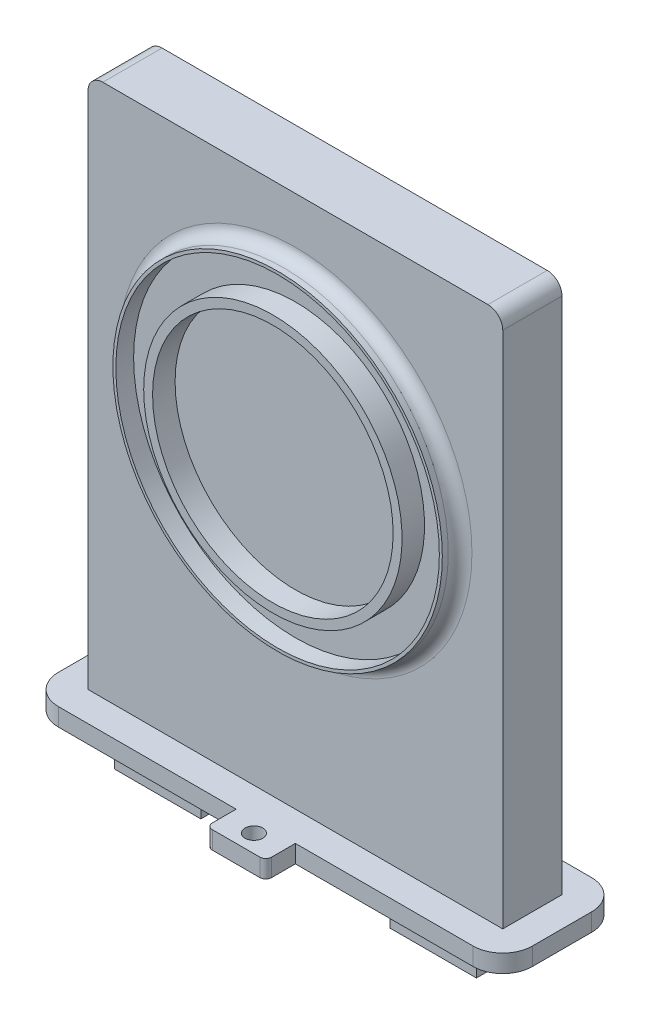
SolidWorks part; units mm, degrees
ref_plane "Front Plane" through (0, 0, 0) normal (0, 0, 1) x (1, 0, 0)
ref_plane "Top Plane" through (0, 0, 0) normal (0, 1, 0) x (1, 0, 0)
ref_plane "Right Plane" through (0, 0, 0) normal (1, 0, 0) x (0, 0, -1)
sketch "Sketch1" plane through (0, 0, 0) normal (0, 0, 1) x (1, 0, 0)
  line L1 (-35, 55.35) -> (35, 55.35)
  line L2 (-35, 55.35) -> (-35, -55.35)
  line L3 (-35, -55.35) -> (35, -55.35)
  line L4 (35, 55.35) -> (35, -55.35)
  line L5 (-35, 55.35) -> (35, -55.35) construction
  line L6 (-35, -55.35) -> (35, 55.35) construction
  point P0 (0, 0)
  dimension "D1" = 70
  dimension "D2" = 110.7
extrude "Boss-Extrude1" add sketch "Sketch1" along normal blind 10
sketch "Sketch3" plane through (0, 0, 0) normal (0, 0, -1) x (-1, 0, 0)
  line L0 (0, -55.35) -> (0, -45) construction
  line L1 (35, -55.35) -> (-35, -55.35) construction
  line L2 (-35, 55.35) -> (35, 55.35) construction
  line L7 (-35, -55.35) -> (-35, 55.35) construction
  line L8 (20.95, -57.2) -> (25.55, -57.2) construction
  line L9 (-20.95, -59.05) -> (-15.95, -59.05)
  line L10 (-30.55, -59.05) -> (-25.55, -59.05)
  line L11 (-30.55, -59.05) -> (-30.55, -61.75)
  line L12 (-30.55, -61.75) -> (-15.95, -61.75)
  line L13 (-15.95, -59.05) -> (-15.95, -61.75)
  line L14 (-30.55, -59.05) -> (-15.95, -61.75) construction
  line L15 (-30.55, -61.75) -> (-15.95, -59.05) construction
  line L16 (-25.55, -55.35) -> (-20.95, -55.35)
  line L17 (-25.55, -55.35) -> (-25.55, -59.05)
  line L19 (-20.95, -55.35) -> (-20.95, -59.05)
  line L20 (-25.55, -55.35) -> (-20.95, -59.05) construction
  line L21 (-25.55, -59.05) -> (-20.95, -55.35) construction
  line L22 (30.55, -59.05) -> (30.55, -61.75)
  line L23 (30.55, -61.75) -> (15.95, -61.75)
  line L24 (15.95, -59.05) -> (15.95, -61.75)
  line L25 (20.95, -59.05) -> (15.95, -59.05)
  line L26 (20.95, -55.35) -> (20.95, -59.05)
  line L27 (25.55, -55.35) -> (20.95, -55.35)
  line L28 (25.55, -55.35) -> (25.55, -59.05)
  line L29 (30.55, -59.05) -> (25.55, -59.05)
  point P5 (0, -50.175)
  point P12 (-23.25, -60.4)
  point P17 (-23.25, -57.2)
  dimension "D1" = 110.7
  dimension "D2" = 11.75
  dimension "D3" = 2.7
  dimension "D4" = 14.6
  dimension "D5" = 4.6
  dimension "D6" = 3.7
extrude "Boss-Extrude3" add sketch "Sketch3" against normal blind 10
sketch "Sketch4" plane through (0, -55.35, 0) normal (0, -1, 0) x (1, 0, 0)
  line L0 (0, 10) -> (0, 0) construction
  line L1 (-20.95, 10) -> (20.95, 10) construction
  line L2 (5, -5) -> (35, -5)
  line L3 (-35, 10) -> (35, 10)
  line L4 (-35, 10) -> (-35, 0)
  line L5 (-35, 0) -> (35, 0)
  line L6 (35, 10) -> (35, 0)
  line L7 (-35, 10) -> (35, 0) construction
  line L8 (-35, 0) -> (35, 10) construction
  line L9 (-35, 15) -> (-5, 15)
  line L10 (-40, 10) -> (-40, 0)
  line L11 (-35, -5) -> (-5, -5)
  line L12 (40, 10) -> (40, 0)
  line L13 (-40, 15) -> (40, -5) construction
  line L14 (-40, -5) -> (40, 15) construction
  line L16 (-5, -5) -> (-5, -9)
  line L17 (-4, -10) -> (4, -10)
  line L18 (5, -5) -> (5, -9)
  line L20 (-40, 5) -> (40, 5) construction
  line L21 (-5, 15) -> (-5, 19)
  line L22 (5, 15) -> (5, 19)
  line L23 (-4, 20) -> (4, 20)
  line L24 (5, 15) -> (35, 15)
  arc A0 (35, 15) -> (40, 10) centre (35, 10) cw
  arc A1 (35, -5) -> (40, 0) centre (35, 0) ccw
  arc A2 (-40, 0) -> (-35, -5) centre (-35, 0) ccw
  arc A3 (-35, 15) -> (-40, 10) centre (-35, 10) ccw
  circle A4 centre (0, -7) radius 1.5
  arc A5 (-5, -9) -> (-4, -10) centre (-4, -9) ccw
  arc A6 (4, -10) -> (5, -9) centre (4, -9) ccw
  circle A7 centre (0, 17) radius 1.5
  arc A8 (-5, 19) -> (-4, 20) centre (-4, 19) cw
  arc A9 (4, 20) -> (5, 19) centre (4, 19) cw
  point P5 (0, 5)
  point P11 (0, 5)
  point P37 (-5, -10)
  dimension "D3" = 5
  dimension "D6" = 3
  dimension "D7" = 1
  dimension "D1" = 20
  dimension "D2" = 80
  dimension "D4" = 5
  dimension "D5" = 10
  dimension "D8" = 3
extrude "Boss-Extrude4" add sketch "Sketch4" against normal blind 3
sketch "Sketch5" plane through (0, 0, 10) normal (0, 0, 1) x (1, 0, 0)
  circle A0 centre (0, 0) radius 27.8
  circle A1 centre (0, 0) radius 27.3
  dimension "D1" = 54.6
  dimension "D2" = 55.6
extrude "Boss-Extrude5" add sketch "Sketch5" along normal blind 3
fillet "Fillet2" radius 2 1 edges at (27.8, 0, 10)
sketch "Sketch10" plane through (0, 0, 10) normal (0, 0, 1) x (1, 0, 0)
  circle A0 centre (0, 0) radius 21.8
  circle A1 centre (0, 0) radius 20.3
  dimension "D1" = 43.6
  dimension "D2" = 40.6
extrude "Boss-Extrude7" add sketch "Sketch10" along normal blind 3.8
sketch "Sketch11" plane through (0, 0, 10) normal (0, 0, 1) x (1, 0, 0)
  line L1 (-35, -52.35) -> (35, -52.35)
  line L2 (-35, -52.35) -> (-35, 37.65)
  line L3 (-35, 37.65) -> (35, 37.65)
  line L4 (35, -52.35) -> (35, 37.65)
  line L9 (-35, -52.35) -> (35, -52.35)
  line L10 (-35, -52.35) -> (-35, 55.35)
  line L11 (-35, 55.35) -> (35, 55.35)
  line L12 (35, -52.35) -> (35, 55.35)
  line M5 (35, -52.35) -> (35, 55.35)
  line M6 (35, 55.35) -> (-35, 55.35)
  line M7 (-35, 55.35) -> (-35, -52.35)
  dimension "D1" = 70
  dimension "D2" = 90
extrude "Cut-Extrude1" cut sketch "Sketch11" against normal up to next contours L3 M7 M5 M6 region at (0, 46.5, 10)
fillet "Fillet3" radius 2.5 2 edges at (35, 37.65, 5) (-35, 37.65, 5)
